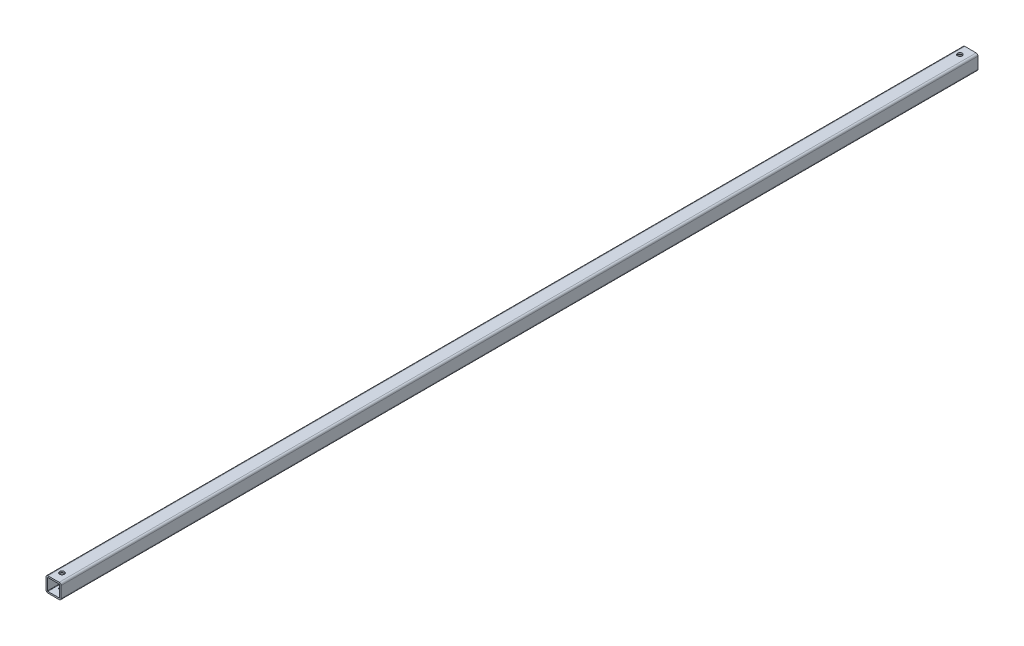
SolidWorks part; units mm, degrees
material "6063-T4"
ref_plane "Front Plane" through (0, 0, 0) normal (0, 0, 1) x (1, 0, 0)
ref_plane "Top Plane" through (0, 0, 0) normal (0, 1, 0) x (1, 0, 0)
ref_plane "Right Plane" through (0, 0, 0) normal (1, 0, 0) x (0, 0, -1)
sketch "Sketch1" plane through (0, 0, 0) normal (0, 0, 1) x (1, 0, 0)
  line L1 (7.5, -10) -> (-7.5, -10)
  line L2 (10, -7.5) -> (10, 7.5)
  line L3 (7.5, 10) -> (-7.5, 10)
  line L4 (-10, -7.5) -> (-10, 7.5)
  line L5 (10, -10) -> (-10, 10) construction
  line L6 (10, 10) -> (-10, -10) construction
  arc A0 (-7.5, 10) -> (-10, 7.5) centre (-7.5, 7.5) ccw
  arc A1 (10, 7.5) -> (7.5, 10) centre (7.5, 7.5) ccw
  arc A2 (7.5, -10) -> (10, -7.5) centre (7.5, -7.5) ccw
  arc A3 (-7.5, -10) -> (-10, -7.5) centre (-7.5, -7.5) cw
  point P0 (0, 0)
  dimension "D2" = 2.5
  dimension "D1" = 20
extrude "Extrude-Thin1" add sketch "Sketch1" along normal mid plane 1219.2 thin thin type one direction reverse wall 2
hole_wizard "1/4 (0.25) Diameter Hole1" positions "Sketch2" profile "Sketch3" hole size "1/4" standard "ANSI Inch"
sketch "Sketch2" plane through (0, 10, 0) normal (0, 1, 0) x (1, 0, 0)
  point P0 (-1.3992, 596.9)
sketch "Sketch3" plane through (-1.3992, 10, -596.9) normal (1, 0, 0) x (0, 0, 1)
  line L0 (0, 0) -> (0, 27.3077)
  line L1 (0, 27.3077) -> (3.175, 25.4)
  line L2 (3.175, 25.4) -> (3.175, 0)
  line L5 (3.175, 0) -> (0, 0)
  line L10 (0, 27.3077) -> (-3.175, 25.4) construction
  line L11 (0, -6.35) -> (0, 107.95) construction
  dimension "Hole Dia." = 6.35
  dimension "Hole Depth" = 25.4
  dimension "Drill Angle" = 118
hole_wizard "1/4 (0.25) Diameter Hole2" positions "Sketch4" profile "Sketch5" hole size "1/4" standard "ANSI Inch"
sketch "Sketch4" plane through (0, 10, 0) normal (0, 1, 0) x (1, 0, 0)
  point P0 (-1.3992, -596.9)
sketch "Sketch5" plane through (-1.3992, 10, 596.9) normal (1, 0, 0) x (0, 0, 1)
  line L0 (0, 0) -> (0, 27.3077)
  line L1 (0, 27.3077) -> (3.175, 25.4)
  line L2 (3.175, 25.4) -> (3.175, 0)
  line L5 (3.175, 0) -> (0, 0)
  line L10 (0, 27.3077) -> (-3.175, 25.4) construction
  line L11 (0, -6.35) -> (0, 107.95) construction
  dimension "Hole Dia." = 6.35
  dimension "Hole Depth" = 25.4
  dimension "Drill Angle" = 118
equation "\"D2@Sketch1\" = \"D5@Extrude-Thin1\" * 1.25"
